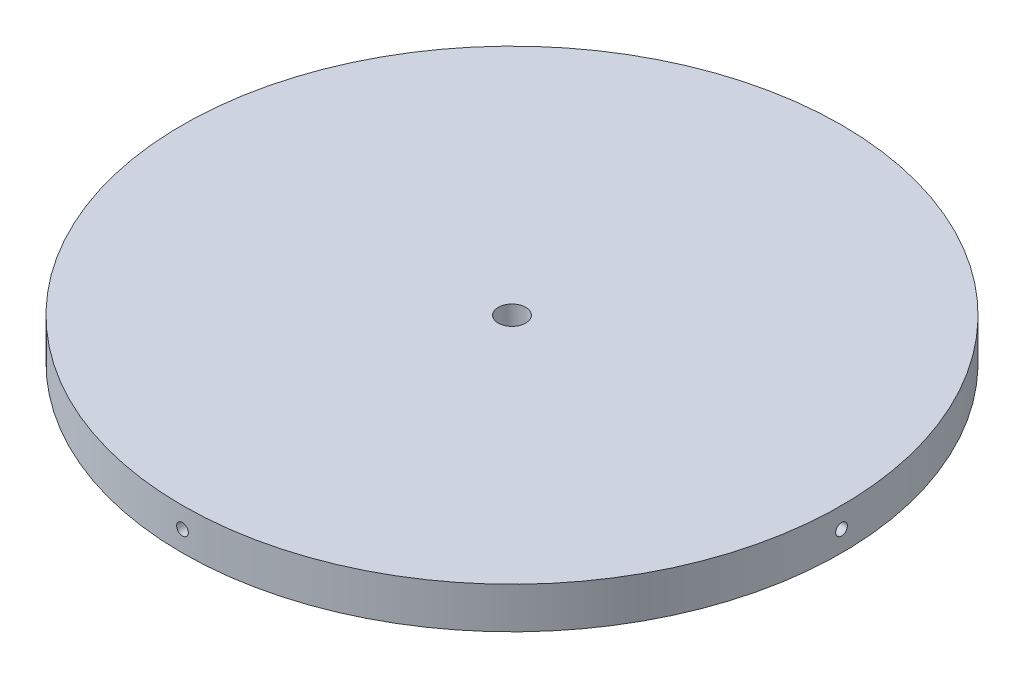
SolidWorks part; units mm, degrees
ref_plane "Front Plane" through (0, 0, 0) normal (0, 0, 1) x (1, 0, 0)
ref_plane "Top Plane" through (0, 0, 0) normal (0, 1, 0) x (1, 0, 0)
ref_plane "Right Plane" through (0, 0, 0) normal (1, 0, 0) x (0, 0, -1)
sketch "Sketch1" plane through (0, 0, 0) normal (0, 1, 0) x (1, 0, 0)
  circle A0 centre (0, 0) radius 76.1746
  circle A1 centre (0, 0) radius 3.175
  dimension "D1" = 152.3492
  dimension "D2" = 6.35
extrude "Boss-Extrude1" add sketch "Sketch1" along normal blind 9.525
ref_plane "Plane1" through (0, 0, -76.1746) normal (0, 0, -1) x (-1, 0, 0)
hole_wizard "Tap Drill for #6-32 Tap1" positions "Sketch2" profile "Sketch3" hole size "#6-32" standard "ANSI Inch"
sketch "Sketch2" plane through (0, 0, -76.1746) normal (0, 0, -1) x (-1, 0, 0)
  point P0 (0, 4.7625)
  dimension "D1" = 4.7625
sketch "Sketch3" plane through (0, 4.7625, -76.1746) normal (1, 0, 0) x (0, 1, 0)
  line L0 (0, 0) -> (0, 10.4647)
  line L1 (0, 10.4647) -> (1.3525, 9.652)
  line L2 (1.3525, 9.652) -> (1.3525, 0)
  line L5 (1.3525, 0) -> (0, 0)
  line L10 (0, 10.4647) -> (-1.3525, 9.652) construction
  line L11 (0, -6.35) -> (0, 107.95) construction
  dimension "Hole Dia." = 2.7051
  dimension "Hole Depth" = 9.652
  dimension "Drill Angle" = 118
pattern_circular "CirPattern1" count 4 over 360 about axis through (0, 9.525, 0) along (0, 1, 0) of "Tap Drill for #6-32 Tap1"
equation "\"AB_Coupler_OD_Length\"= 1in"
equation "\"AB_Coupling_Section_Length\"= 0.375in"
equation "\"AB_Coupler_Length\"= \"AB_Coupler_OD_Length\" + \"AB_Coupling_Section_Length\" * 2"
equation "\"Cutout_Angle\" = 80"
equation "\"AB_Coupler_Num_Screws\"= 6"
equation "\"Num_Cutouts\" = 3"
equation "\"AB_Coupler_OD\"= 6.17in"
equation "\"AB_Coupler_ID\"= 5.75in"
equation "\"AB_Coupler_Surface_Diameter\"= 5.998in"
equation "\"AB_Coupling_Screw_Diameter\"= 0.1065in"
equation "\"Aft_Section_Length\"= 40in"
equation "\"Aft_Lower_Length\"= 20in"
equation "\"Aft_Upper_Length\"= \"Aft_Section_Length\" - \"Aft_Lower_Length\" - \"AB_Coupler_OD_Length\""
equation "\"Mid_Coupler_Length\" = 10in"
equation "\"Lead_Screw_Dist\" = 2.25in"
equation "\"Lead_Screw_Diam\" = (27/64)*1in"
equation "\"Lead_Screw_Length\" = (\"Mid_Coupler_Length\" + 2*0.375in + 2*0.5in)"
equation "\"Bodytube_OD\" = 6.17in"
equation "\"Bodytube_ID\" = 5.998in"
equation "\"Paddle_Pin_Radius\" = 2.55in"
equation "\"D1@Sketch1\"=\"AB_Coupler_Surface_Diameter\""
equation "\"D2@Sketch1\"=1/4in"
equation "\"D1@Sketch2\"=.375/2"
